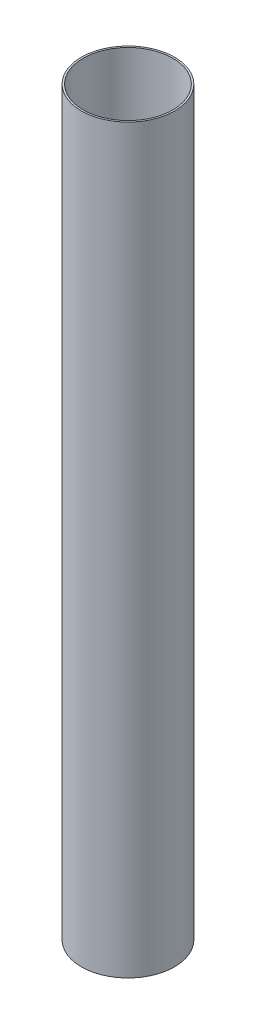
SolidWorks part; units mm, degrees
ref_plane "Front Plane" through (0, 0, 0) normal (0, 0, 1) x (1, 0, 0)
ref_plane "Top Plane" through (0, 0, 0) normal (0, 1, 0) x (1, 0, 0)
ref_plane "Right Plane" through (0, 0, 0) normal (1, 0, 0) x (0, 0, -1)
sketch "Sketch1" plane through (0, 0, 0) normal (0, 1, 0) x (1, 0, 0)
  circle A0 centre (0, 0) radius 38.1
  circle A1 centre (0, 0) radius 39.6
  dimension "D1" = 76.2
  dimension "D2" = 79.2
  dimension "D3" = 1.5
extrude "Boss-Extrude1" add sketch "Sketch1" along normal blind 315 and the other way blind 315
